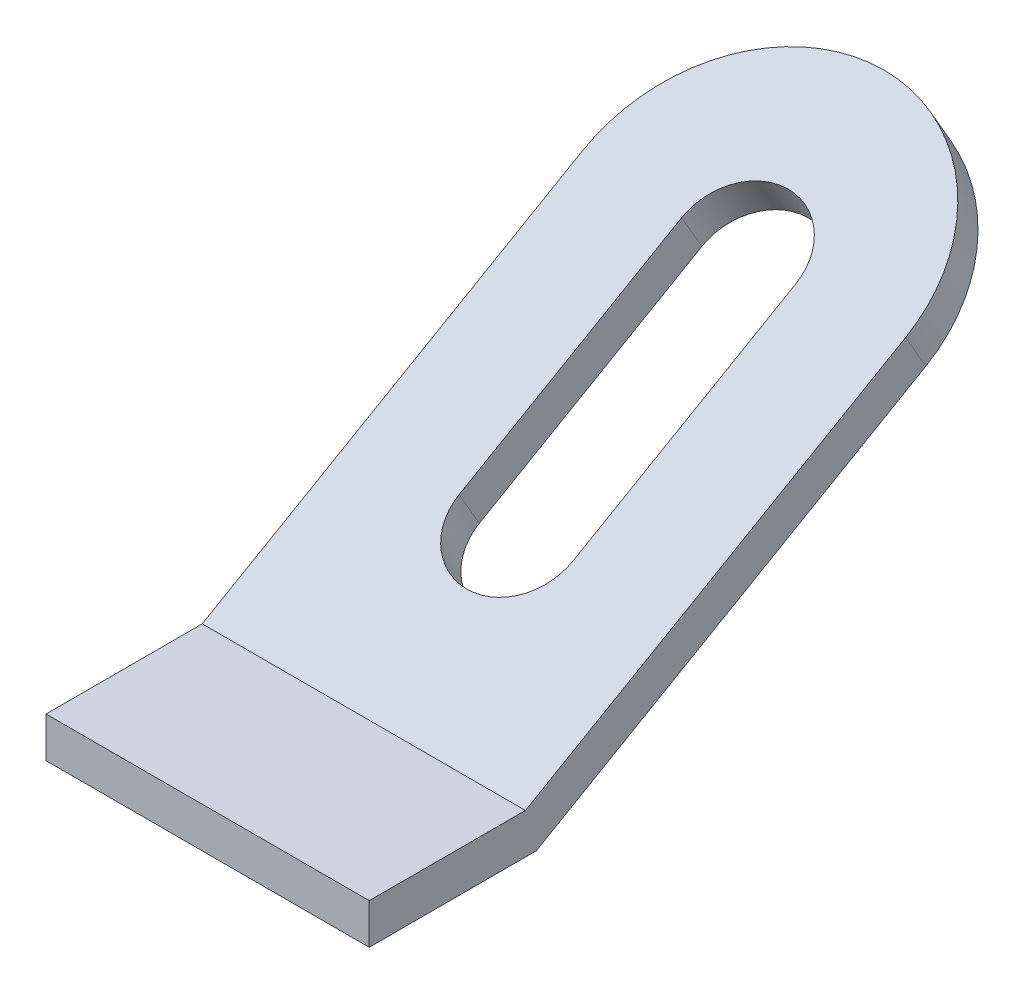
SolidWorks part; units mm, degrees
ref_plane "Alzado" through (0, 0, 0) normal (0, 0, 1) x (1, 0, 0)
ref_plane "Planta" through (0, 0, 0) normal (0, 1, 0) x (1, 0, 0)
ref_plane "Vista lateral" through (0, 0, 0) normal (1, 0, 0) x (0, 0, -1)
sketch "Croquis9" plane through (0, 0, 0) normal (1, 0, 0) x (0, 0, -1)
  line L0 (0, 0) -> (-1, 0) construction
  line L1 (0, 0) -> (3.2476, 1.875) construction
  line L2 (0.0625, -0.1083) -> (3.3101, 1.7667) construction
  line L3 (0, 0.125) -> (-1, 0.125) construction
  line L4 (-0.0625, 0.1083) -> (3.1851, 1.9833) construction
  line L5 (0, -0.125) -> (-1, -0.125) construction
  line L6 (0.0625, -0.1083) -> (-0.0625, 0.1083) construction
  line L7 (3.3101, 1.7667) -> (3.1851, 1.9833)
  line L8 (0, 0.125) -> (0, -0.125) construction
  line L9 (-1, 0.125) -> (-1, -0.125)
  line L10 (-1, 0.125) -> (-0.0335, 0.125)
  line L11 (-0.0335, 0.125) -> (3.1851, 1.9833)
  line L12 (3.3101, 1.7667) -> (0.0335, -0.125)
  line L13 (0.0335, -0.125) -> (-1, -0.125)
  dimension "D1" = 0.125
  dimension "D2" = 0.125
extrude "Saliente-Extruir3" add sketch "Croquis9" along normal blind 2
fillet "Redondeo2" radius 1 2 edges at (0, 1.875, -3.2476) (2, 1.875, -3.2476)
sketch "Croquis10" plane through (0, 0.1083, 0.0625) normal (0, 0.866, 0.5) x (1, 0, 0)
  line L0 (1, 3.75) -> (1, 0.0335) construction
  line L1 (2, 0.0335) -> (0, 0.0335) construction
  line L2 (1, 1.1223) -> (1, 2.7124) construction
  line L3 (0.6466, 1.1223) -> (0.6466, 2.7124)
  line L4 (1.3534, 1.1223) -> (1.3534, 2.7124)
  arc A0 (0.6466, 1.1223) -> (1.3534, 1.1223) centre (1, 1.1223) ccw
  arc A1 (1.3534, 2.7124) -> (0.6466, 2.7124) centre (1, 2.7124) ccw
  point P7 (1, 1.9174)
extrude "Cortar-Extruir1" cut sketch "Croquis10" against normal up to next
